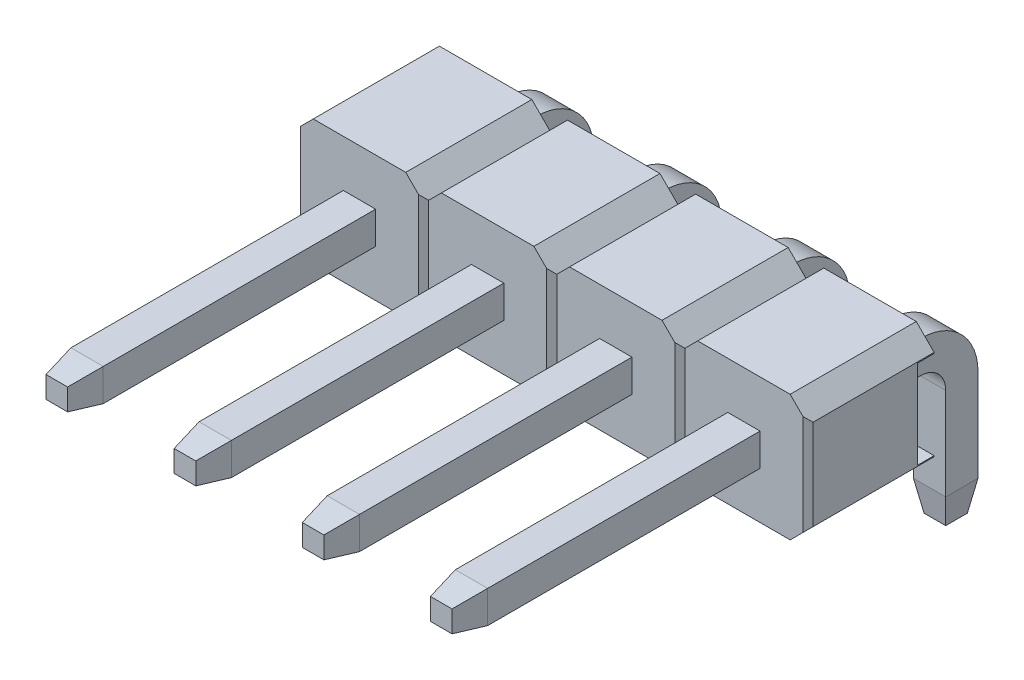
SolidWorks part; units mm, degrees
ref_plane "Front Plane" through (0, 0, 0) normal (0, 0, 1) x (1, 0, 0)
ref_plane "Top Plane" through (0, 0, 0) normal (0, 1, 0) x (1, 0, 0)
ref_plane "Right Plane" through (0, 0, 0) normal (1, 0, 0) x (0, 0, -1)
sketch "Sketch1" plane through (0, 0, 0) normal (0, 0, 1) x (1, 0, 0)
  line L0 (-1.27, 0.8964) -> (-0.9164, 1.25)
  line L1 (-0.9164, 1.25) -> (0.9164, 1.25)
  line L2 (-1.27, 0.8964) -> (-1.27, -0.8964)
  line L3 (-0.9164, -1.25) -> (0.9164, -1.25)
  line L4 (1.27, 0.8964) -> (1.27, -0.8964)
  line L5 (-1.27, -0.8964) -> (-0.9164, -1.25)
  line L6 (0.9164, -1.25) -> (1.27, -0.8964)
  line L7 (1.27, 0.8964) -> (0.9164, 1.25)
  point P0 (1.27, -1.25)
  point P7 (-1.27, 1.25)
  point P10 (-1.27, -1.25)
  point P15 (1.27, 1.25)
  dimension "D5" = 0.25
  dimension "D1" = 2.54
  dimension "D2" = 2.5
  dimension "D3" = 1.27
  dimension "D4" = 1.25
  dimension "D6" = 0.25
  dimension "D7" = 0.25
  dimension "D8" = 0.25
extrude "Extrude1" add sketch "Sketch1" along normal blind 1.25 and the other way blind 1.25
sketch "Sketch4" plane through (0, 0, 0) normal (0, 1, 0) x (1, 0, 0)
  line L0 (-1.27, -1.15) -> (-1.17, -1.25)
  line L1 (-1.17, -1.25) -> (-1.27, -1.25)
  line L2 (-1.27, -1.25) -> (-1.27, -1.15)
  line L3 (1.17, -1.25) -> (1.27, -1.15)
  line L4 (1.27, -1.15) -> (1.27, -1.25)
  line L5 (1.27, -1.25) -> (1.17, -1.25)
extrude "Cut-Extrude3" cut sketch "Sketch4" against normal through all and the other way through all
pattern_linear "LPattern4" count 3 spacing 2.54 along (-1, 0, 0) count 2 spacing 2.54 along (1, 0, 0) of "Extrude1", "Cut-Extrude3"
sketch "Sketch2" plane through (0, 0, 0) normal (1, 0, 0) x (0, -1, 0)
  line L1 (-0.8764, 1.25) -> (0.8764, 1.25)
  line L2 (-0.8764, 1.25) -> (-0.8764, 0.92)
  line L3 (-0.8764, 0.92) -> (0.8764, 0.92)
  line L4 (0.8764, 1.25) -> (0.8764, 0.92)
  dimension "D1" = 0.33
extrude "Cut-Extrude1" cut sketch "Sketch2" against normal through all and the other way through all
sketch "Sketch3" plane through (0, 0, 0) normal (1, 0, 0) x (0, 0, -1)
  line L0 (-7.25, 0) -> (2.75, 0)
  line L1 (2.75, 0) -> (2.75, -3.25)
  line L2 (-1.25, -1.25) -> (1.25, -1.25) construction
  line L3 (1.25, 1.25) -> (1.25, 0.8964) construction
  dimension "D1" = 6
  dimension "D2" = 1.5
  dimension "D3" = 2
extrude "Extrude-Thin1" add sketch "Sketch3" along normal blind 0.32 and the other way blind 0.32 thin thin type mid plane wall 0.64
pattern_linear "LPattern5" count 2 spacing 2.54 along (1, 0, 0) count 3 spacing 2.54 along (-1, 0, 0) of "Extrude-Thin1"
chamfer "Chamfer2" distance 0.6 angle 10 32 edges at (0.32, 0, 7.25) (0, -0.32, 7.25) (-0.32, 0, 7.25) (0, 0.32, 7.25) (0.32, -3.25, -2.75) (0, -3.25, -3.07) (-0.32, -3.25, -2.75) (0, -3.25, -2.43) (2.86, -3.25, -2.75) (2.54, -3.25, -3.07) (2.22, -3.25, -2.75) (2.54, -3.25, -2.43) (-4.76, -3.25, -2.75) (-5.08, -3.25, -3.07) (-5.4, -3.25, -2.75) (-5.08, -3.25, -2.43) (-2.22, -3.25, -2.75) (-2.54, -3.25, -3.07) (-2.86, -3.25, -2.75) (-2.54, -3.25, -2.43) (2.86, 0, 7.25) (2.54, -0.32, 7.25) (2.22, 0, 7.25) (2.54, 0.32, 7.25) (-2.22, 0, 7.25) (-2.54, -0.32, 7.25) (-2.86, 0, 7.25) (-2.54, 0.32, 7.25) (-4.76, 0, 7.25) (-5.08, -0.32, 7.25) (-5.4, 0, 7.25) (-5.08, 0.32, 7.25) first distance on face at (0.32, 0, 4.25) first distance on face at (0, -0.32, 4.25) first distance on face at (-0.32, 0, 4.25) first distance on face at (0, 0.32, 4.25) first distance on face at (0.32, -1.0833, -2.14) first distance on face at (0, -1.465, -3.07) first distance on face at (-0.32, -1.0833, -2.14) first distance on face at (0, -1.785, -2.43) first distance on face at (2.86, -1.0833, -2.14) first distance on face at (2.54, -1.465, -3.07) first distance on face at (2.22, -1.0833, -2.14) first distance on face at (2.54, -1.785, -2.43) first distance on face at (-4.76, -1.0833, -2.14) first distance on face at (-5.08, -1.465, -3.07) first distance on face at (-5.4, -1.0833, -2.14) first distance on face at (-5.08, -1.785, -2.43) first distance on face at (-2.22, -1.0833, -2.14) first distance on face at (-2.54, -1.465, -3.07) first distance on face at (-2.86, -1.0833, -2.14) first distance on face at (-2.54, -1.785, -2.43) first distance on face at (2.86, 0, 4.25) first distance on face at (2.54, -0.32, 4.25) first distance on face at (2.22, 0, 4.25) first distance on face at (2.54, 0.32, 4.25) first distance on face at (-2.22, 0, 4.25) first distance on face at (-2.54, -0.32, 4.25) first distance on face at (-2.86, 0, 4.25) first distance on face at (-2.54, 0.32, 4.25) first distance on face at (-4.76, 0, 4.25) first distance on face at (-5.08, -0.32, 4.25) first distance on face at (-5.4, 0, 4.25) first distance on face at (-5.08, 0.32, 4.25)
fillet "Fillet1" radius 0.5 4 edges at (0, -0.32, -2.43) (-5.08, -0.32, -2.43) (-2.54, -0.32, -2.43) (2.54, -0.32, -2.43)
fillet "Fillet2" radius 1.14 4 edges at (0, 0.32, -3.07) (-5.08, 0.32, -3.07) (-2.54, 0.32, -3.07) (2.54, 0.32, -3.07)
ref_plane "Board Plane" through (0, -1.5, 0) normal (0, 1, 0) x (-1, 0, 0)
sketch "Component_Outline" plane through (0, -1.5, 0) normal (0, 1, 0) x (-1, 0, 0)
  line L0 (6.35, 1.15) -> (6.35, -1.25)
  line L1 (6.35, -1.25) -> (5.4, -1.25)
  line L2 (5.9964, -1.25) -> (4.1636, -1.25) construction
  line L3 (5.4, -0.92) -> (5.4, -1.93) construction
  line L4 (5.4, -1.25) -> (5.4, -3.07)
  line L5 (5.4, -3.07) -> (-2.86, -3.07)
  line L6 (-2.86, -3.07) -> (-2.86, -1.25)
  line L7 (-2.86, -0.92) -> (-2.86, -1.93) construction
  line L8 (-1.6236, -1.25) -> (-3.4564, -1.25) construction
  line L9 (-2.86, -1.25) -> (-3.81, -1.25)
  line L10 (-3.81, -1.25) -> (-3.81, 1.15)
  line L11 (-3.81, 1.15) -> (-3.71, 1.25)
  line L12 (-3.71, 1.25) -> (-1.37, 1.25)
  line L13 (-1.37, 1.25) -> (-1.27, 1.15)
  line L14 (-1.27, 1.15) -> (-1.17, 1.25)
  line L15 (-1.17, 1.25) -> (1.17, 1.25)
  line L16 (1.17, 1.25) -> (1.27, 1.15)
  line L17 (1.27, 1.15) -> (1.37, 1.25)
  line L18 (1.37, 1.25) -> (3.71, 1.25)
  line L19 (3.71, 1.25) -> (3.81, 1.15)
  line L20 (3.81, 1.15) -> (3.91, 1.25)
  line L21 (3.91, 1.25) -> (6.25, 1.25)
  line L22 (6.25, 1.25) -> (6.35, 1.15)
  line L23 (-2.7542, -2.9642) -> (-2.3258, -2.5358)
  line L27 (-2.7542, -2.9642) -> (-2.3258, -2.9642)
  line L28 (-2.7542, -2.5358) -> (-2.7542, -2.9642)
  line L29 (-2.3258, -2.5358) -> (-2.7542, -2.5358)
  line L30 (-2.3258, -2.9642) -> (-2.3258, -2.5358)
  line L31 (-2.7542, -2.9642) -> (-2.3258, -2.9642) construction
  line L32 (-2.7542, -2.5358) -> (-2.7542, -2.9642) construction
  line L33 (-2.3258, -2.5358) -> (-2.7542, -2.5358) construction
  line L34 (-2.3258, -2.9642) -> (-2.3258, -2.5358) construction
  point P46 (-2.54, -2.75)
  dimension "D1" = 0
